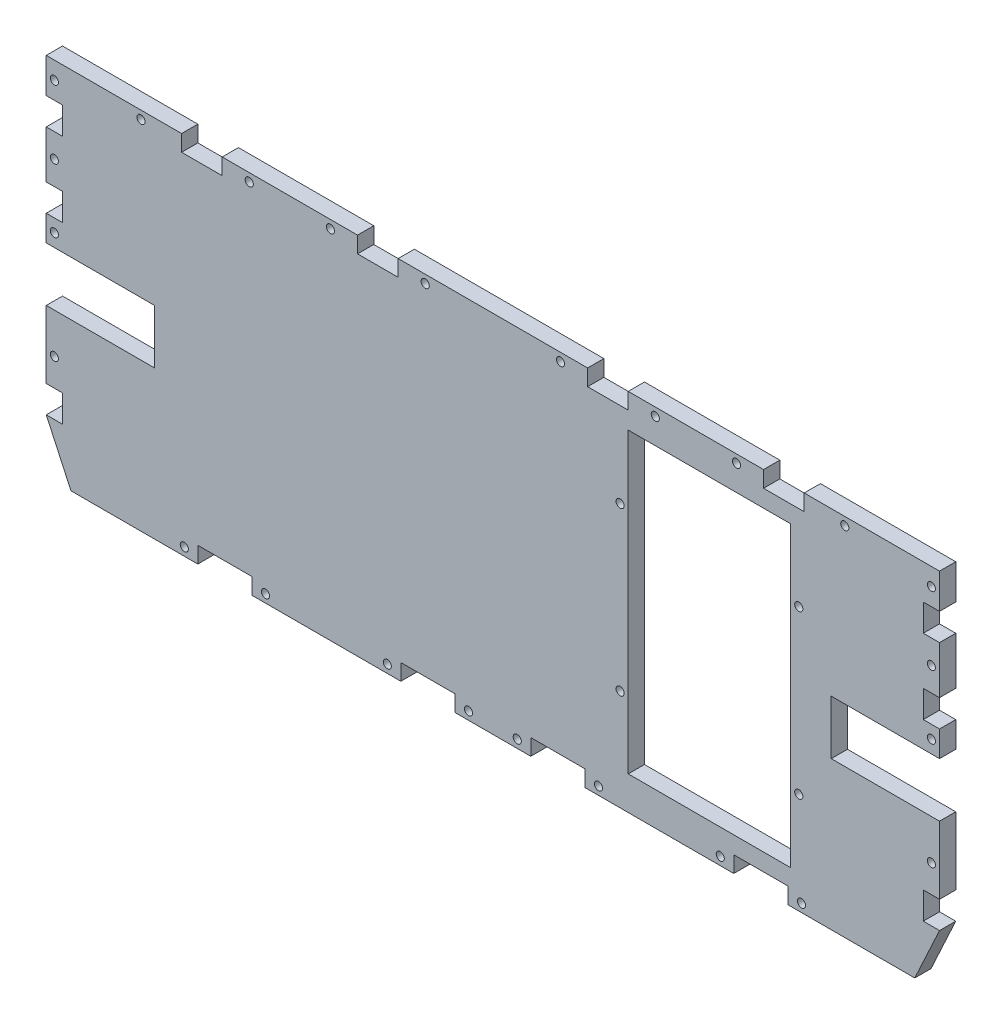
SolidWorks part; units mm, degrees
ref_plane "Plan de face" through (0, 0, 0) normal (0, 0, 1) x (1, 0, 0)
ref_plane "Plan de dessus" through (0, 0, 0) normal (0, 1, 0) x (1, 0, 0)
ref_plane "Plan de droite" through (0, 0, 0) normal (1, 0, 0) x (0, 0, -1)
sketch "Esquisse1" plane through (0, 0, 0) normal (0, 0, 1) x (1, 0, 0)
  line L0 (0, 124.9429) -> (0, -204.46) construction
  line L1 (-165, 96.73) -> (165, 96.73)
  line L2 (165, 96.73) -> (165, -18.27)
  line L3 (165, -18.27) -> (123, -109.0224)
  line L4 (123, -109.0224) -> (-123, -109.0224)
  line L5 (-211.9802, 0) -> (248.5953, 0) construction
  line L6 (-123, -109.0224) -> (-165, -18.27)
  line L7 (-165, -18.27) -> (-165, 96.73)
  dimension "D2" = 165
  dimension "D3" = 330
  dimension "D4" = 100
  dimension "D5" = 115
  dimension "D6" = 100
  dimension "D7" = 246
  dimension "D8" = 205.7524
  dimension "D9" = 96.73
  dimension "D10" = 115
extrude "Boss.-Extru.1" add sketch "Esquisse1" along normal blind 6
sketch "Esquisse3" plane through (0, 0, 0) normal (0, 0, -1) x (-1, 0, 0)
  line L0 (165, 96.73) -> (165, -18.27) construction
  line L1 (165, -18.27) -> (159, -18.27)
  line L2 (165, -18.27) -> (165, -8.27)
  line L3 (165, -8.27) -> (159, -8.27)
  line L4 (159, -18.27) -> (159, -8.27)
  line L5 (123, -109.0224) -> (-123, -109.0224) construction
  line L6 (165, 73.8526) -> (159, 73.8526)
  line L7 (165, 73.8526) -> (165, 83.8526)
  line L8 (165, 83.8526) -> (159, 83.8526)
  line L9 (159, 73.8526) -> (159, 83.8526)
  line L10 (-14, -38.02) -> (-14, -32.02)
  line L11 (109, -38.02) -> (89, -38.02)
  line L12 (109, -38.02) -> (109, -32.02)
  line L13 (109, -32.02) -> (89, -32.02)
  line L14 (-159, 46.23) -> (-159, 56.23)
  line L15 (0, -209.4812) -> (0, 177.1799) construction
  line L16 (-110, 84.355) -> (-50, 84.355)
  line L17 (-165, 56.23) -> (-159, 56.23)
  line L18 (89, -38.02) -> (89, -32.02)
  line L19 (34, -38.02) -> (14, -38.02)
  line L20 (34, -38.02) -> (34, -32.02)
  line L21 (34, -32.02) -> (14, -32.02)
  line L22 (-159, 73.8526) -> (-159, 83.8526)
  line L23 (-165, 83.8526) -> (-159, 83.8526)
  line L24 (-165, 73.8526) -> (-165, 83.8526)
  line L25 (-165, 73.8526) -> (-159, 73.8526)
  line L26 (-159, -18.27) -> (-159, -8.27)
  line L27 (-165, -8.27) -> (-159, -8.27)
  line L28 (-165, -18.27) -> (-165, -8.27)
  line L29 (-165, -18.27) -> (-159, -18.27)
  line L30 (-165, 96.73) -> (165, 96.73) construction
  line L31 (115, 96.73) -> (100, 96.73)
  line L32 (115, 96.73) -> (115, 90.73)
  line L33 (115, 90.73) -> (100, 90.73)
  line L34 (100, 96.73) -> (100, 90.73)
  line L35 (-35, 96.73) -> (-35, 90.73)
  line L36 (50, 96.73) -> (35, 96.73)
  line L37 (50, 96.73) -> (50, 90.73)
  line L38 (50, 90.73) -> (35, 90.73)
  line L39 (35, 96.73) -> (35, 90.73)
  line L40 (-50, 90.73) -> (-35, 90.73)
  line L41 (-50, 96.73) -> (-50, 90.73)
  line L42 (-50, 96.73) -> (-35, 96.73)
  line L43 (-100, 96.73) -> (-100, 90.73)
  line L44 (-115, 90.73) -> (-100, 90.73)
  line L45 (-115, 96.73) -> (-115, 90.73)
  line L46 (-115, 96.73) -> (-100, 96.73)
  line L47 (-165, 46.23) -> (-165, 56.23)
  line L48 (14, -38.02) -> (14, -32.02)
  line L49 (-34, -32.02) -> (-14, -32.02)
  line L50 (-34, -38.02) -> (-34, -32.02)
  line L51 (-34, -38.02) -> (-14, -38.02)
  line L52 (165, 46.23) -> (159, 46.23)
  line L53 (165, 46.23) -> (165, 56.23)
  line L54 (165, 56.23) -> (159, 56.23)
  line L55 (159, 46.23) -> (159, 56.23)
  line L56 (-165, 46.23) -> (-159, 46.23)
  line L57 (-89, -38.02) -> (-89, -32.02)
  line L58 (-109, -32.02) -> (-89, -32.02)
  line L59 (-109, -38.02) -> (-109, -32.02)
  line L60 (-109, -38.02) -> (-89, -38.02)
  line L61 (-165, -18.27) -> (-165, 96.73) construction
  line L62 (-110, 84.355) -> (-110, -25.645)
  line L63 (-110, -25.645) -> (-50, -25.645)
  line L64 (-50, 84.355) -> (-50, -25.645)
  line L66 (-165, 36.73) -> (-125, 36.73)
  line L67 (-165, 36.73) -> (-165, 16.73)
  line L68 (-165, 16.73) -> (-125, 16.73)
  line L69 (-125, 36.73) -> (-125, 16.73)
  line L70 (125, 36.73) -> (125, 16.73)
  line L71 (165, 16.73) -> (125, 16.73)
  line L72 (165, 36.73) -> (165, 16.73)
  line L73 (165, 36.73) -> (125, 36.73)
  dimension "D1" = 10
  dimension "D2" = 6
  dimension "D3" = 6
  dimension "D4" = 10
  dimension "D5" = 6
  dimension "D6" = 20
  dimension "D7" = 60
  dimension "D8" = 55
  dimension "D9" = 12.8774
  dimension "D10" = 15
  dimension "D11" = 15
  dimension "D12" = 50
  dimension "D13" = 50
  dimension "D14" = 6
  dimension "D15" = 110
  dimension "D16" = 56
  dimension "D17" = 15
  dimension "D18" = 6
  dimension "D19" = 10
  dimension "D20" = 40.5
  dimension "D21" = 6
  dimension "D22" = 6
  dimension "D23" = 20
  dimension "D24" = 71.0024
  dimension "D25" = 71.0024
  dimension "D26" = 60
  dimension "D27" = 20
  dimension "D28" = 40
  dimension "D29" = 6.375
extrude "Enlèv. mat.-Extru.2" cut sketch "Esquisse3" against normal blind 6
sketch "Esquisse4" plane through (0, 0, 0) normal (0, 0, -1) x (-1, 0, 0)
  line L0 (159, 73.8526) -> (165, 73.8526) construction
  line L1 (115, 90.73) -> (115, 96.73) construction
  line L2 (120.102, -35.02) -> (4.7601, -35.02) construction
  line L3 (14, -32.02) -> (14, -38.02) construction
  line L4 (34, -38.02) -> (34, -32.02) construction
  line L5 (89, -32.02) -> (89, -38.02) construction
  line L6 (115, 96.73) -> (165, 96.73) construction
  line L7 (109, -38.02) -> (109, -32.02) construction
  line L8 (165, 73.8526) -> (165, 56.23) construction
  line L9 (-120.102, -35.02) -> (-4.7601, -35.02) construction
  line L10 (165, 96.73) -> (165, 83.8526) construction
  line L11 (143.8632, 93.73) -> (0, 93.73) construction
  line L12 (50, 96.73) -> (100, 96.73) construction
  line L13 (-113, 100.4555) -> (-113, -24.6685) construction
  line L14 (100, 96.73) -> (100, 90.73) construction
  line L15 (50, 90.73) -> (50, 96.73) construction
  line L16 (35, 96.73) -> (35, 90.73) construction
  line L17 (0, 142.2997) -> (0, -202.2086) construction
  line L18 (-162, -8.8123) -> (-162, 103.5881) construction
  line L19 (-80, 84.355) -> (-80, -25.645) construction
  line L20 (159, 46.23) -> (165, 46.23) construction
  line L21 (165, -8.27) -> (159, -8.27) construction
  line L22 (162, -8.8123) -> (162, 103.5881) construction
  line L24 (-110, 84.355) -> (-110, -25.645) construction
  line L25 (-50, 84.355) -> (-110, 84.355) construction
  line L26 (-110, -25.645) -> (-50, -25.645) construction
  circle A0 centre (162, 1.92) radius 1.5
  circle A1 centre (114, -35.02) radius 1.5
  circle A2 centre (162, 65.0426) radius 1.5
  circle A3 centre (84, -35.02) radius 1.5
  circle A4 centre (39, -35.02) radius 1.5
  circle A5 centre (162, 90.29) radius 1.5
  circle A6 centre (9, -35.02) radius 1.5
  circle A7 centre (-9, -35.02) radius 1.5
  circle A8 centre (-39, -35.02) radius 1.5
  circle A9 centre (-84, -35.02) radius 1.5
  circle A10 centre (130, 93.73) radius 1.5
  circle A11 centre (-114, -35.02) radius 1.5
  circle A12 centre (90, 93.73) radius 1.5
  circle A13 centre (-162, 41.48) radius 1.5
  circle A14 centre (60, 93.73) radius 1.5
  circle A15 centre (25, 93.73) radius 1.5
  circle A17 centre (-113, 59.355) radius 1.5
  circle A18 centre (-25, 93.73) radius 1.5
  circle A19 centre (-60, 93.73) radius 1.5
  circle A20 centre (-90, 93.73) radius 1.5
  circle A21 centre (-130, 93.73) radius 1.5
  circle A22 centre (-162, 90.29) radius 1.5
  circle A23 centre (-162, 65.0426) radius 1.5
  circle A24 centre (-162, 1.92) radius 1.5
  circle A26 centre (-113, -0.645) radius 1.5
  circle A27 centre (-47, -0.645) radius 1.5
  circle A29 centre (-47, 59.355) radius 1.5
  circle A33 centre (162, 41.48) radius 1.5
  dimension "D1" = 3
  dimension "D3" = 3
  dimension "D10" = 3
  dimension "D11" = 3
  dimension "D12" = 3
  dimension "D13" = 5
  dimension "D14" = 5
  dimension "D18" = 3
  dimension "D19" = 3
  dimension "D29" = 3
  dimension "D30" = 25
  dimension "D31" = 3
  dimension "D33" = 3
  dimension "D34" = 3
  dimension "D35" = 4.75
  dimension "D40" = 10
  dimension "D5" = 10.19
  dimension "D8" = 15
  dimension "D15" = 5
  dimension "D16" = 5
  dimension "D20" = 3
  dimension "D17" = 3
  dimension "D21" = 60
  dimension "D22" = 3
  dimension "D23" = 3
  dimension "D9" = 3
  dimension "D6" = 8.81
  dimension "D7" = 6.44
  dimension "D24" = 3
  dimension "D26" = 3
  dimension "D28" = 3
  dimension "D38" = 10
  dimension "D41" = 25
  dimension "D42" = 10
extrude "Enlèv. mat.-Extru.3" cut sketch "Esquisse4" against normal blind 6
sketch "Esquisse5" plane through (0, 0, 0) normal (0, 0, -1) x (-1, 0, 0)
  line L0 (50, 96.73) -> (100, 96.73) construction
  line L1 (209.7155, -38.02) -> (-246.3297, -38.02)
  line L2 (209.7155, -38.02) -> (209.7155, -174.249)
  line L3 (209.7155, -174.249) -> (-246.3297, -174.249)
  line L4 (-246.3297, -38.02) -> (-246.3297, -174.249)
  dimension "D1" = 134.75
extrude "Enlèv. mat.-Extru.4" cut sketch "Esquisse5" against normal blind 6
